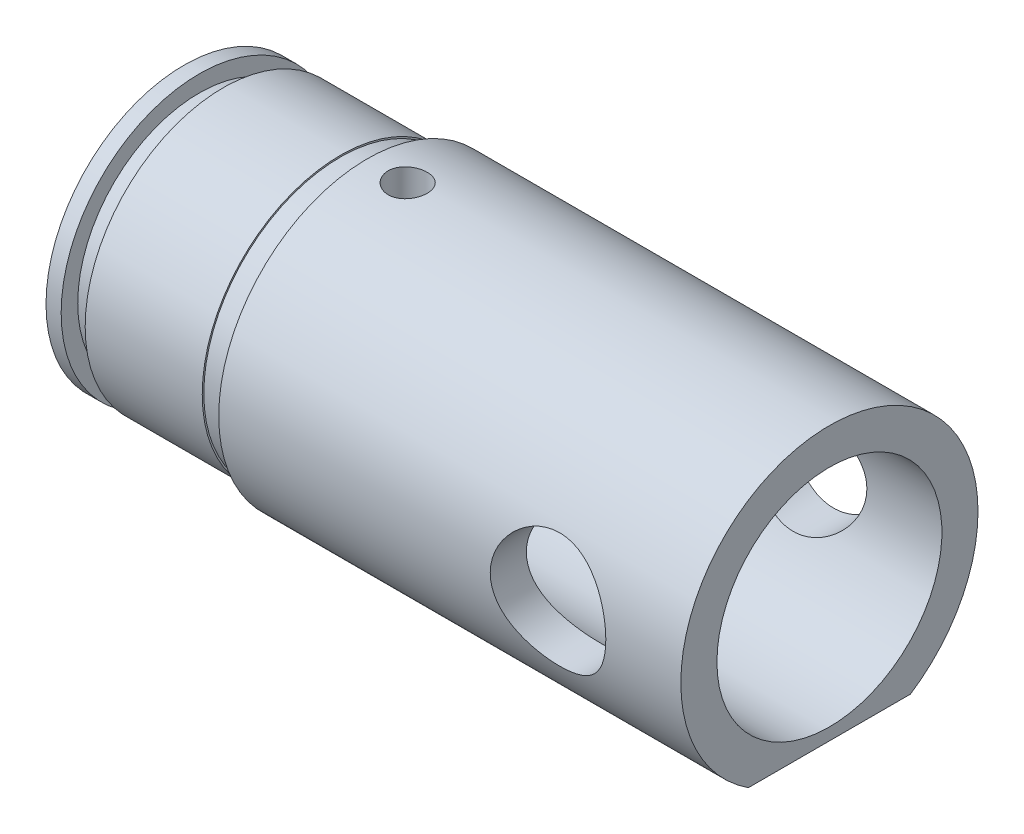
SolidWorks part; units mm, degrees
material "6061-T6 (SS)"
ref_plane "Front Plane" through (0, 0, 0) normal (0, 0, 1) x (1, 0, 0)
ref_plane "Top Plane" through (0, 0, 0) normal (0, 1, 0) x (1, 0, 0)
ref_plane "Right Plane" through (0, 0, 0) normal (1, 0, 0) x (0, 0, -1)
sketch "Sketch1" plane through (0, 0, 0) normal (0, 0, 1) x (1, 0, 0)
  line L0 (-164.2485, 0) -> (152.8805, 0) construction
  line L1 (-8.1915, 2.413) -> (-23.9903, 2.413)
  line L2 (-27.305, 0) -> (-23.9903, 0)
  line L3 (27.305, 12.573) -> (27.305, 9.5186)
  line L4 (27.305, 12.573) -> (-11.7983, 12.573)
  line L5 (-11.7983, 11.5506) -> (-11.7983, 12.573)
  line L6 (-11.7983, 11.5506) -> (-14.0843, 11.5506)
  line L7 (-14.0843, 11.5506) -> (-14.0843, 11.684)
  line L8 (-14.0843, 11.684) -> (-23.9903, 11.684)
  line L9 (-23.9903, 11.684) -> (-23.9903, 10.2806)
  line L10 (-23.9903, 10.2806) -> (-26.0223, 10.2806)
  line L11 (-26.0223, 10.2806) -> (-26.0223, 11.684)
  line L12 (-26.0223, 11.684) -> (-27.305, 11.684)
  line L13 (-27.305, 11.684) -> (-27.305, 0)
  line L14 (27.305, 9.5186) -> (-4.5466, 9.5186)
  line L15 (-23.9903, 2.413) -> (-23.9903, 0)
  line L17 (-4.5466, 9.5186) -> (-8.1915, 2.413)
  dimension "D2" = 12.573
  dimension "D3" = 11.684
  dimension "D4" = 39.1033
  dimension "D6" = 2.286
  dimension "D7" = 9.906
  dimension "D9" = 2.032
  dimension "D11" = 3.0543
  dimension "D12" = 31.8516
revolve "Revolve2" add sketch "Sketch1" angle 360 about L0
sketch "Sketch2" plane through (0, 0, 0) normal (0, 0, 1) x (1, 0, 0)
  line L0 (0, 0) -> (12.9808, 0) construction
  line L2 (-9.2583, -12.573) -> (-9.2583, -10.795)
  line L3 (-9.2583, -10.795) -> (2.4257, -10.795)
  line L4 (-11.7983, -12.573) -> (27.305, -12.573) construction
  line L7 (2.4257, -10.795) -> (2.4257, -12.573)
sketch "Sketch3" plane through (0, 0, 0) normal (0, 0, 1) x (1, 0, 0)
  line L0 (27.305, 12.573) -> (17.145, 12.573) construction
  line L1 (27.305, 12.573) -> (-11.7983, 12.573) construction
  line L2 (0, 0) -> (18.788, 0) construction
  line L6 (27.305, -10.541) -> (27.305, -12.573)
  line L7 (17.145, -12.573) -> (27.305, -10.541)
extrude "Cut-Extrude4" cut sketch "Sketch2" against normal through all and the other way through all flip side to cut
extrude "Cut-Extrude5" cut sketch "Sketch3" against normal through all and the other way through all flip side to cut
ref_plane "Plane1" through (0, 12.573, 0) normal (0, 1, 0) x (-1, 0, 0)
sketch "Sketch4" plane through (0, 12.573, 0) normal (0, 1, 0) x (-1, 0, 0)
  line L0 (27.305, 0) -> (8.382, 0) construction
  line L1 (27.305, -11.684) -> (27.305, 11.684) construction
  circle A0 centre (8.382, 0) radius 1.651
  dimension "D2" = 3.302
  dimension "D1" = 18.923
extrude "Cut-Extrude6" cut sketch "Sketch4" against normal blind 4.572
sketch "Sketch5" plane through (0, 0, 0) normal (0, 0, 1) x (1, 0, 0)
  circle A0 centre (16.0655, 0) radius 4.8895
extrude "Cut-Extrude7" cut sketch "Sketch5" against normal through all and the other way through all
